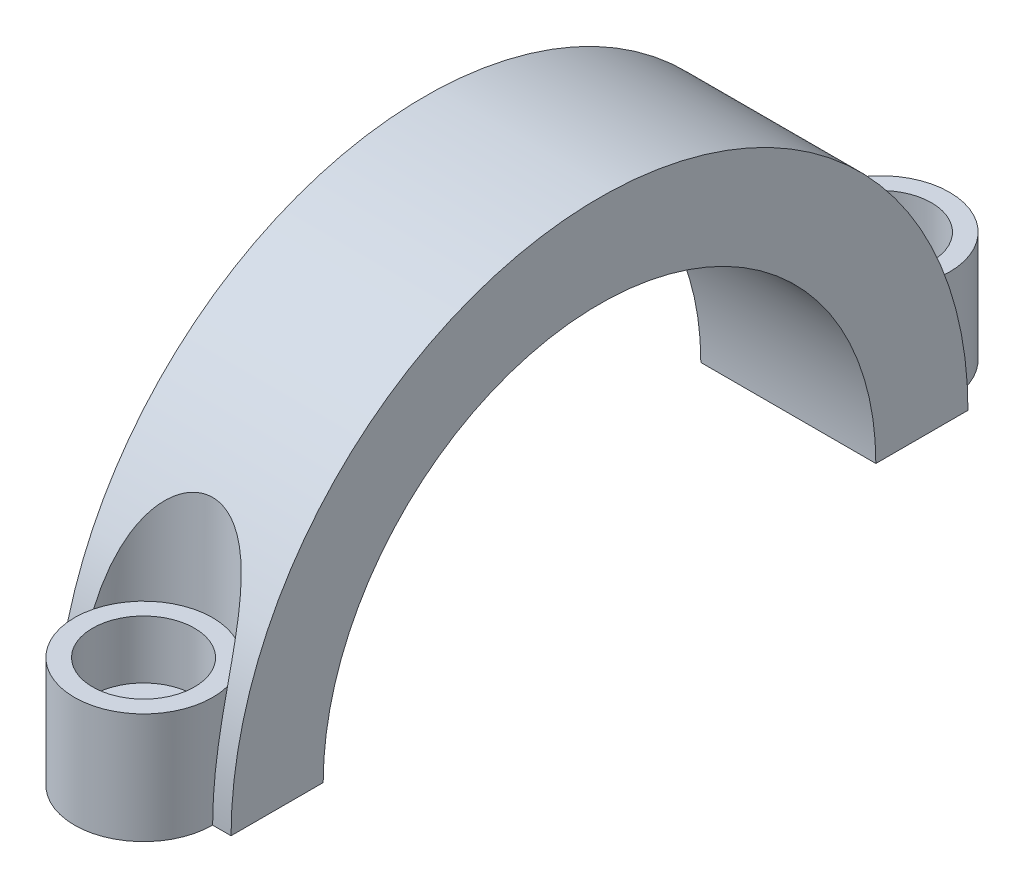
SolidWorks part; units mm, degrees
ref_plane "Front Plane" through (0, 0, 0) normal (0, 0, 1) x (1, 0, 0)
ref_plane "Top Plane" through (0, 0, 0) normal (0, 1, 0) x (1, 0, 0)
ref_plane "Right Plane" through (0, 0, 0) normal (1, 0, 0) x (0, 0, -1)
sketch "Sketch1" plane through (0, 0, 0) normal (1, 0, 0) x (0, 0, -1)
  line L0 (0, 44.2032) -> (0, -50.7157) construction
  line L1 (-73.1022, 0) -> (103.0595, 0) construction
  line L2 (38.1, 0) -> (50.8, 0)
  line L7 (-38.1, 0) -> (-50.8, 0)
  arc A0 (38.1, 0) -> (-38.1, 0) centre (0, 0) ccw
  arc A1 (50.8, 0) -> (-50.8, 0) centre (0, 0) ccw
  dimension "D1" = 76.2
  dimension "D2" = 101.6
extrude "Boss-Extrude1" add sketch "Sketch1" along normal mid plane 24.13
sketch "Sketch2" plane through (0, 0, 0) normal (0, -1, 0) x (1, 0, 0)
  line L0 (34.8304, 0) -> (-30.4714, 0) construction
  line L1 (0, 70.3108) -> (0, -64.9308) construction
  circle A0 centre (0, -50.8) radius 3.4
  circle A1 centre (0, -50.8) radius 7.025
  circle A2 centre (0, -50.8) radius 9.525
  circle A3 centre (0, 50.8) radius 3.4
  circle A4 centre (0, 50.8) radius 7.025
  circle A5 centre (0, 50.8) radius 9.525
  point P12 (0, -50.8)
  point P14 (0, -50.8)
  point P15 (0, 0)
  point P16 (0, -50.8)
  line M2 (-12.065, -50.8) -> (12.065, -50.8)
  dimension "D2" = 6.8
  dimension "D3" = 14.05
  dimension "D4" = 19.05
  dimension "D1" = 120.65
  dimension "D5" = 9.525
extrude "Cut-Extrude1" cut sketch "Sketch2<6>" against normal blind 68.25 contours A2 A1 M2 | A2 A1 M2 | A1 A0 M2 | A1 A0 M2 | A0 M2 | A0 M2 | A3 | A4 A3 | A5 A4 region at (0, 0, -49.357) region at (0, 0, -54.2521) region at (0, 0, -47.3479) region at (0, 0, -52.243) region at (8.275, 0, -51.013) region at (0, 0, -43.562) region at (0, 0, 50.8) region at (-6.8263, 0, 50.8) region at (-9.2556, 0, 50.8)
sketch "Sketch2<6>" plane through (0, 0, 0) normal (0, -1, 0) x (1, 0, 0) same geometry as "Sketch2"
extrude "Boss-Extrude2" add sketch "Sketch2" against normal blind 15.25 contours A2 A1 M2 | A2 A1 M2 | A5 A4 region at (8.275, 0, -51.013) region at (0, 0, -43.562) region at (-9.2556, 0, 50.8)
extrude "Boss-Extrude3" add sketch "Sketch2<8>" against normal blind 7.25 contours A4 A3 | A1 A0 M2 | A1 A0 M2 region at (0, 0, -54.2521) region at (0, 0, -47.3479) region at (-6.8263, 0, 50.8)
sketch "Sketch2<8>" plane through (0, 0, 0) normal (0, -1, 0) x (1, 0, 0) same geometry as "Sketch2"
